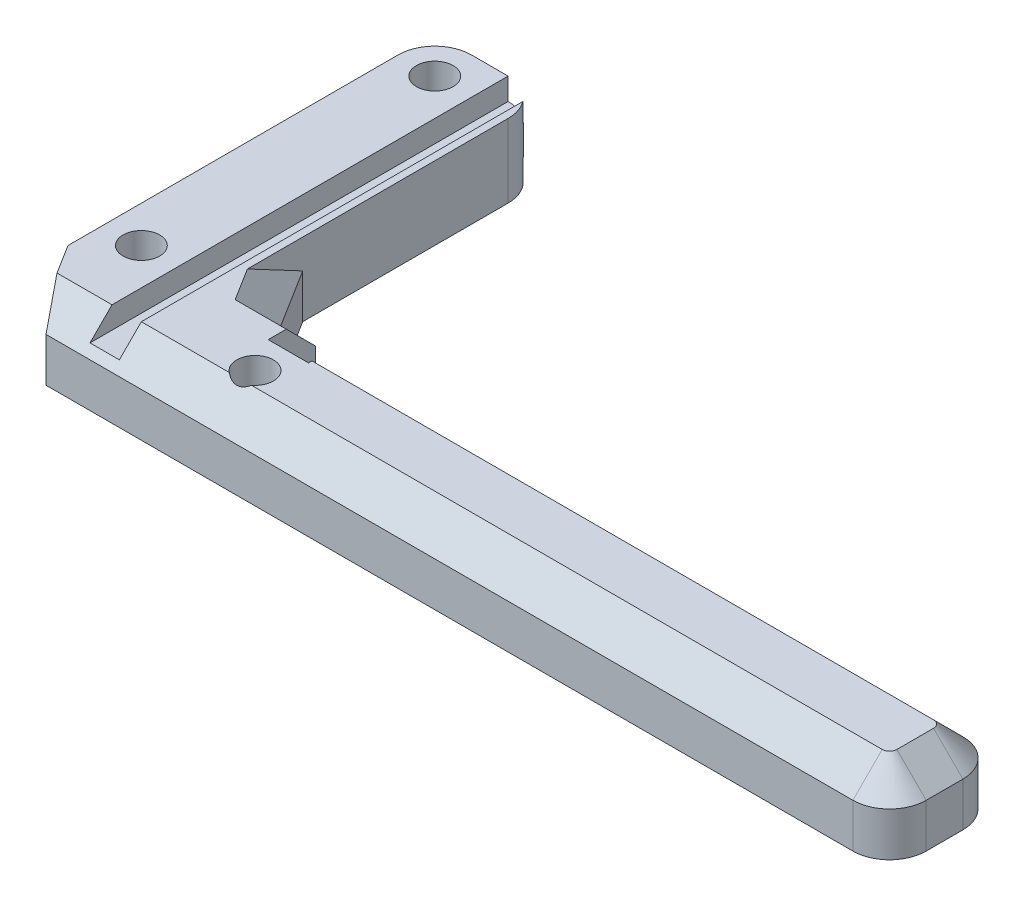
SolidWorks part; units mm, degrees
ref_plane "Front Plane" through (0, 0, 0) normal (0, 0, 1) x (1, 0, 0)
ref_plane "Top Plane" through (0, 0, 0) normal (0, 1, 0) x (1, 0, 0)
ref_plane "Right Plane" through (0, 0, 0) normal (1, 0, 0) x (0, 0, -1)
sketch "Sketch1" plane through (0, 0, 0) normal (0, 1, 0) x (1, 0, 0)
  line L0 (0, -25) -> (0, 25)
  line L1 (0, 25) -> (15, 25)
  line L2 (15, 25) -> (15, -8)
  line L4 (5, 25) -> (5, -25) construction
  line L7 (120, -18) -> (35, -18)
  line L9 (15, -8) -> (20, -16)
  line L13 (25.01, -22.22) -> (30.01, -22.22) construction
  line L16 (24.76, -16) -> (24.76, -22.47)
  line L17 (24.76, -22.47) -> (30.26, -22.47)
  line L18 (30.26, -22.47) -> (30.26, -18)
  line L19 (24.76, -14.8332) -> (24.76, -22.47) construction
  line L20 (30.26, -22.47) -> (30.26, -14.8332) construction
  line L21 (20, -16) -> (24.76, -16)
  line L22 (25.01, -14.8332) -> (25.01, -22.22) construction
  line L23 (30.01, -22.22) -> (30.01, -14.8332) construction
  line L25 (24.76, -16) -> (30.26, -16) construction
  line L26 (27.51, -16) -> (27.51, -13.7726) construction
  line L27 (0, -25) -> (5, -33)
  line L28 (5, -33) -> (120, -33)
  line L29 (120, -33) -> (120, -18)
  line L30 (30.26, -18) -> (35, -18)
  circle A0 centre (5, 20) radius 2.5
  circle A1 centre (5, -20) radius 2.5
  point P3 (0, 0)
  dimension "D3" = 5
  dimension "D1" = 50
  dimension "D2" = 15
  dimension "D4" = 40
  dimension "D5" = 20
  dimension "D6" = 5.5
  dimension "D7" = 41
  dimension "D8" = 20
  dimension "D9" = 15
  dimension "D10" = 5
  dimension "D11" = 5
  dimension "D13" = 8
  dimension "D14" = 27.51
  dimension "D15" = 5
  dimension "D16" = 8
  dimension "D17" = 0.25
extrude "Boss-Extrude1" add sketch "Sketch1" along normal blind 10
sketch "Sketch2" plane through (0, 10, 0) normal (0, 1, 0) x (1, 0, 0)
  line L0 (10, 25) -> (10, -36.321)
  line L1 (10, -36.321) -> (14, -36.321)
  line L2 (14, -36.321) -> (14, 25)
  line L3 (14, 25) -> (10, 25)
  line L4 (15, 25) -> (0, 25) construction
  line L5 (0, 25) -> (0, -25) construction
  dimension "D1" = 4
  dimension "D2" = 10
extrude "Cut-Extrude1" cut sketch "Sketch2" against normal blind 3
fillet "Fillet1" radius 5 4 edges at (120, 5, 33) (120, 5, 18) (0, 5, -25) (15, 5, -25)
chamfer "Chamfer2" distance 4 angle 45 5 edges at (118.5355, 10, 31.5355) (120, 10, 25.5) (118.5355, 10, 19.4645) (72.63, 10, 18) (64.5, 10, 33)
chamfer "Chamfer3" distance 4 angle 45 2 edges at (22.38, 10, 16) (17.5, 10, 12)
sketch "Sketch3" plane through (0, 10, 0) normal (0, 1, 0) x (1, 0, 0)
  line L0 (0, 20) -> (0, -25) construction
  line L2 (10, 25) -> (5, 25) construction
  circle A0 centre (27.5, -27) radius 2.5
  dimension "D1" = 5
  dimension "D2" = 27.5
  dimension "D3" = 52
extrude "Cut-Extrude2" cut sketch "Sketch3" against normal blind 10
